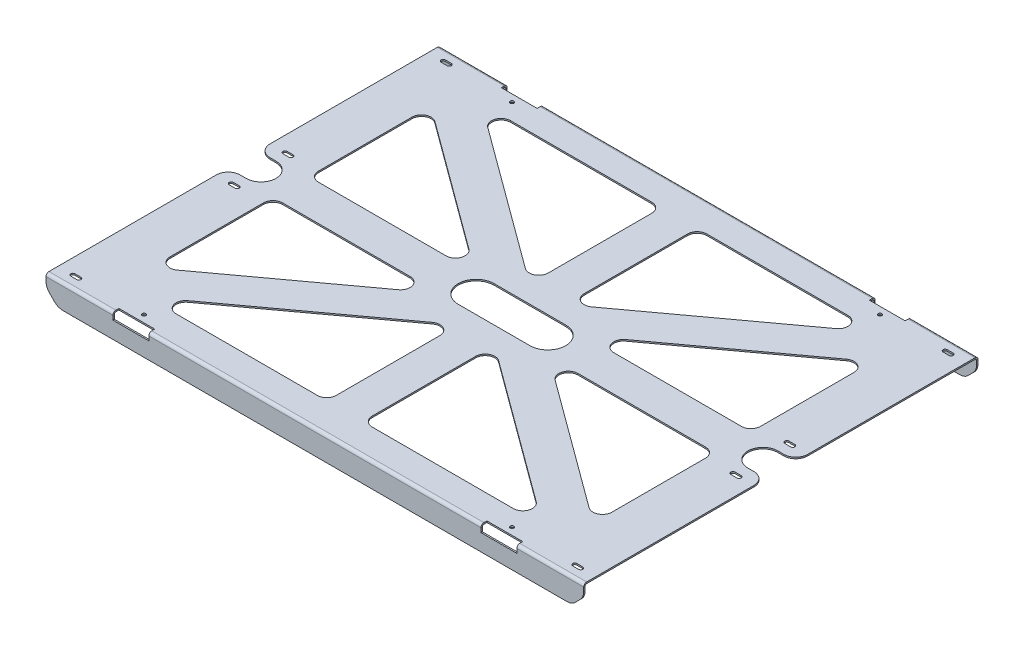
SolidWorks part; units mm, degrees
note: The reader was unsure of these and kept them because the rebuilt part matched: flange length of "Edge-Flange1".
material "1023 Carbon Steel Sheet (SS)"
ref_plane "Front Plane" through (0, 0, 0) normal (0, 0, 1) x (1, 0, 0)
ref_plane "Top Plane" through (0, 0, 0) normal (0, 1, 0) x (1, 0, 0)
ref_plane "Right Plane" through (0, 0, 0) normal (1, 0, 0) x (0, 0, -1)
sketch "Sketch1" plane through (0, 0, 0) normal (0, 1, 0) x (1, 0, 0)
  line L0 (-225, 165) -> (0, 0) construction
  line L1 (-225, -165) -> (225, -165)
  line L2 (-225, -165) -> (-225, -22.5)
  line L3 (-225, 165) -> (225, 165)
  line L4 (225, -165) -> (225, -22.5)
  line L5 (0, 165) -> (0, -165) construction
  line L6 (-225, 0) -> (225, 0) construction
  line L7 (-15, 132) -> (-15, 45.3883)
  line L8 (-172.2691, 107.7296) -> (-65.5259, 29.4512)
  line L9 (-145.8378, 125.5488) -> (-27.7309, 38.9371)
  line L10 (-185, 23) -> (-185, 101.2784)
  line L11 (-185, 125) -> (185, 125) construction
  line L12 (-185, -125) -> (-185, 125) construction
  line L13 (-185, -125) -> (185, -125) construction
  line L14 (185, -125) -> (185, 125) construction
  line L15 (-216.1295, 177.0961) -> (8.8705, 12.0961) construction
  line L16 (-233.8705, 152.9039) -> (-8.8705, -12.0961) construction
  line L17 (-141.1068, 140) -> (-23, 140)
  line L18 (-177, 15) -> (-70.2568, 15)
  line L19 (-15, 165) -> (-15, -165) construction
  line L20 (-225, 15) -> (225, 15) construction
  line L21 (177, 15) -> (70.2568, 15)
  line L22 (185, 23) -> (185, 101.2784)
  line L23 (172.2691, 107.7296) -> (65.5259, 29.4512)
  line L24 (145.8378, 125.5488) -> (27.7309, 38.9371)
  line L25 (141.1068, 140) -> (23, 140)
  line L26 (15, 132) -> (15, 45.3883)
  line L27 (-177, -15) -> (-70.2568, -15)
  line L28 (-185, -23) -> (-185, -101.2784)
  line L29 (-172.2691, -107.7296) -> (-65.5259, -29.4512)
  line L30 (-15, -132) -> (-15, -45.3883)
  line L31 (-145.8378, -125.5488) -> (-27.7309, -38.9371)
  line L32 (-141.1068, -140) -> (-23, -140)
  line L33 (15, -132) -> (15, -45.3883)
  line L34 (141.1068, -140) -> (23, -140)
  line L35 (145.8378, -125.5488) -> (27.7309, -38.9371)
  line L36 (172.2691, -107.7296) -> (65.5259, -29.4512)
  line L37 (185, -23) -> (185, -101.2784)
  line L38 (177, -15) -> (70.2568, -15)
  line L39 (-30, 0) -> (30, 0) construction
  line L40 (-30, 15) -> (30, 15)
  line L41 (-30, -15) -> (30, -15)
  line L42 (-225, 22.5) -> (-225, 165)
  line L43 (-225, -165) -> (-225, 165) construction
  line L44 (225, 22.5) -> (225, 165)
  line L45 (225, -165) -> (225, 165) construction
  line L46 (210, -12.5) -> (215, -12.5)
  line L47 (210, 12.5) -> (215, 12.5)
  line L48 (-212.5, 22.5) -> (-207.5, 22.5) construction
  line L49 (-212.5, 155) -> (-207.5, 155) construction
  line L50 (-212.5, 156.75) -> (-207.5, 156.75)
  line L51 (-212.5, 153.25) -> (-207.5, 153.25)
  line L52 (-212.5, -155) -> (-207.5, -155) construction
  line L53 (-212.5, -156.75) -> (-207.5, -156.75)
  line L54 (-212.5, -153.25) -> (-207.5, -153.25)
  line L55 (212.5, -155) -> (207.5, -155) construction
  line L56 (212.5, -156.75) -> (207.5, -156.75)
  line L57 (212.5, -153.25) -> (207.5, -153.25)
  line L58 (-212.5, 24.25) -> (-207.5, 24.25)
  line L59 (-212.5, 20.75) -> (-207.5, 20.75)
  line L60 (-212.5, -22.5) -> (-207.5, -22.5) construction
  line L61 (212.5, 155) -> (207.5, 155) construction
  line L62 (212.5, 156.75) -> (207.5, 156.75)
  line L63 (212.5, 153.25) -> (207.5, 153.25)
  line L64 (-210, 12.5) -> (-215, 12.5)
  line L65 (-210, -12.5) -> (-215, -12.5)
  line L66 (-212.5, -20.75) -> (-207.5, -20.75)
  line L67 (-212.5, -24.25) -> (-207.5, -24.25)
  line L68 (207.5, 22.5) -> (212.5, 22.5) construction
  line L69 (207.5, 24.25) -> (212.5, 24.25)
  line L70 (207.5, 20.75) -> (212.5, 20.75)
  line L71 (207.5, -22.5) -> (212.5, -22.5) construction
  line L72 (207.5, -20.75) -> (212.5, -20.75)
  line L73 (207.5, -24.25) -> (212.5, -24.25)
  arc A0 (-185, 23) -> (-177, 15) centre (-177, 23) ccw
  arc A1 (-172.2691, 107.7296) -> (-185, 101.2784) centre (-177, 101.2784) ccw
  arc A2 (-65.5259, 29.4512) -> (-70.2568, 15) centre (-70.2568, 23) cw
  arc A3 (-27.7309, 38.9371) -> (-15, 45.3883) centre (-23, 45.3883) ccw
  arc A4 (-15, 132) -> (-23, 140) centre (-23, 132) ccw
  arc A5 (-145.8378, 125.5488) -> (-141.1068, 140) centre (-141.1068, 132) cw
  arc A6 (185, 23) -> (177, 15) centre (177, 23) cw
  arc A7 (172.2691, 107.7296) -> (185, 101.2784) centre (177, 101.2784) cw
  arc A8 (65.5259, 29.4512) -> (70.2568, 15) centre (70.2568, 23) ccw
  arc A9 (145.8378, 125.5488) -> (141.1068, 140) centre (141.1068, 132) ccw
  arc A10 (15, 132) -> (23, 140) centre (23, 132) cw
  arc A11 (27.7309, 38.9371) -> (15, 45.3883) centre (23, 45.3883) cw
  arc A12 (-185, -23) -> (-177, -15) centre (-177, -23) cw
  arc A13 (-172.2691, -107.7296) -> (-185, -101.2784) centre (-177, -101.2784) cw
  arc A14 (-65.5259, -29.4512) -> (-70.2568, -15) centre (-70.2568, -23) ccw
  arc A15 (-15, -132) -> (-23, -140) centre (-23, -132) cw
  arc A16 (-27.7309, -38.9371) -> (-15, -45.3883) centre (-23, -45.3883) cw
  arc A17 (-145.8378, -125.5488) -> (-141.1068, -140) centre (-141.1068, -132) ccw
  arc A18 (27.7309, -38.9371) -> (15, -45.3883) centre (23, -45.3883) ccw
  arc A19 (15, -132) -> (23, -140) centre (23, -132) ccw
  arc A20 (145.8378, -125.5488) -> (141.1068, -140) centre (141.1068, -132) cw
  arc A21 (65.5259, -29.4512) -> (70.2568, -15) centre (70.2568, -23) cw
  arc A22 (172.2691, -107.7296) -> (185, -101.2784) centre (177, -101.2784) ccw
  arc A23 (185, -23) -> (177, -15) centre (177, -23) ccw
  arc A24 (-30, 15) -> (-30, -15) centre (-30, 0) ccw
  arc A25 (30, -15) -> (30, 15) centre (30, 0) ccw
  arc A26 (-210, -12.5) -> (-210, 12.5) centre (-210, 0) ccw
  arc A27 (-215, -12.5) -> (-225, -22.5) centre (-215, -22.5) ccw
  arc A28 (-215, 12.5) -> (-225, 22.5) centre (-215, 22.5) cw
  arc A29 (215, -12.5) -> (225, -22.5) centre (215, -22.5) cw
  arc A30 (210, -12.5) -> (210, 12.5) centre (210, 0) cw
  arc A31 (215, 12.5) -> (225, 22.5) centre (215, 22.5) ccw
  arc A32 (-212.5, 24.25) -> (-212.5, 20.75) centre (-212.5, 22.5) ccw
  arc A33 (-207.5, 20.75) -> (-207.5, 24.25) centre (-207.5, 22.5) ccw
  arc A34 (-212.5, 156.75) -> (-212.5, 153.25) centre (-212.5, 155) ccw
  arc A35 (-207.5, 153.25) -> (-207.5, 156.75) centre (-207.5, 155) ccw
  arc A36 (-212.5, -156.75) -> (-212.5, -153.25) centre (-212.5, -155) cw
  arc A37 (-207.5, -153.25) -> (-207.5, -156.75) centre (-207.5, -155) cw
  arc A38 (212.5, -156.75) -> (212.5, -153.25) centre (212.5, -155) ccw
  arc A39 (207.5, -153.25) -> (207.5, -156.75) centre (207.5, -155) ccw
  arc A40 (-212.5, -20.75) -> (-212.5, -24.25) centre (-212.5, -22.5) ccw
  arc A41 (-207.5, -24.25) -> (-207.5, -20.75) centre (-207.5, -22.5) ccw
  arc A42 (212.5, 156.75) -> (212.5, 153.25) centre (212.5, 155) cw
  arc A43 (207.5, 153.25) -> (207.5, 156.75) centre (207.5, 155) cw
  arc A44 (207.5, 24.25) -> (207.5, 20.75) centre (207.5, 22.5) ccw
  arc A45 (212.5, 20.75) -> (212.5, 24.25) centre (212.5, 22.5) ccw
  arc A46 (207.5, -20.75) -> (207.5, -24.25) centre (207.5, -22.5) ccw
  arc A47 (212.5, -24.25) -> (212.5, -20.75) centre (212.5, -22.5) ccw
  point P0 (0, 0)
  point P95 (0, 0)
  point P103 (-210, -22.5)
  point P104 (-225, -12.5)
  point P117 (-197.5, 0)
  point P120 (-210, 155)
  point P127 (-210, -155)
  point P134 (210, -155)
  point P139 (-210, 22.5)
  point P148 (210, 155)
  point P153 (-225, 12.5)
  point P157 (0, 0)
  point P158 (210, -22.5)
  point P165 (210, 22.5)
  point P174 (216.5035, 22.5)
  point P175 (0, 0)
  point P176 (0, 0)
  point P177 (-244.1151, 153.25)
  point P178 (244.8311, 22.5)
  point P179 (-231.402, 22.5)
  point P186 (0, 0)
  point P187 (0, 0)
  point P188 (0, 0)
  point P189 (-237.0247, -22.5)
  point P190 (0, 0)
  point P191 (-190.9514, 155)
  point P192 (0, 0)
  point P193 (0, 0)
  dimension "D9" = 8
  dimension "D10" = 15
  dimension "D11" = 60
  dimension "D12" = 25
  dimension "D13" = 15
  dimension "D15" = 2
  dimension "D16" = 15
  dimension "D17" = 1.75
  dimension "D18" = 5
  dimension "D21" = 10
  dimension "D1" = 450
  dimension "D2" = 330
  dimension "D6" = 25
  dimension "D14" = 2
  dimension "D19" = 10
  dimension "D3" = 40
  dimension "D4" = 15
  dimension "D5" = 15
  dimension "D7" = 15
  dimension "D8" = 15
base flange "Base-Flange1" sketch "Sketch1" thickness 1.2141 reverse thickness direction no parameters "D1"=1.27
edge flange "Edge-Flange1" sketch "Sketch10" flange profiles "Sketch10", "Sketch11" flange angle 90 flange length 20 flange position material inside bend radius 1.27 thickness 1.2141 relief rectangular parameters "D6"=10, "D8"=1
sketch "Sketch10" plane through (0, -1.2141, 165) normal (0, 0, 1) x (-1, 0, 0)
  line L2 (-225, 0) -> (-225, 18.7859)
  line L3 (-225, 18.7859) -> (225, 18.7859)
  line L4 (225, 18.7859) -> (225, 0)
  line L5 (225, 0) -> (-225, 0) construction
  line L6 (225, 0) -> (-225, 0)
sketch "Sketch11" plane through (0, -1.2141, -165) normal (0, 0, -1) x (1, 0, 0)
  line L0 (225, 0) -> (-225, 0) construction
  line L1 (225, 0) -> (-225, 0)
  line L2 (-225, 0) -> (-225, 18.7859)
  line L3 (-225, 18.7859) -> (225, 18.7859)
  line L4 (225, 18.7859) -> (225, 0)
bend "EdgeBend1" bend radius 1.27 bend angle 90 parameters "D5"=1
bend "EdgeBend2" bend radius 1.27 bend angle 90 parameters "D5"=2
chamfer "Chamfer1" distance 10 angle 45 4 edges at (225, -20, -164.3929) (-225, -20, -164.3929) (-225, -20, 164.3929) (225, -20, 164.3929)
fillet "Fillet1" radius 10 8 edges at (-225, -10, -164.3929) (-215, -20, -164.3929) (215, -20, -164.3929) (225, -10, -164.3929) (225, -10, 164.3929) (215, -20, 164.3929) (-215, -20, 164.3929) (-225, -10, 164.3929)
sketch "Sketch12" plane through (0, 0, 0) normal (0, 1, 0) x (1, 0, 0)
  line L1 (154, 154) -> (-154, 154) construction
  line L2 (154, 154) -> (154, -154) construction
  line L3 (154, -154) -> (-154, -154) construction
  line L4 (-154, 154) -> (-154, -154) construction
  line L5 (0, -154) -> (0, 154) construction
  line L6 (154, 0) -> (-154, 0) construction
  circle A0 centre (154, -154) radius 1.55
  circle A1 centre (-154, -154) radius 1.55
  circle A2 centre (-154, 154) radius 1.55
  circle A3 centre (154, 154) radius 1.55
  point P0 (0, 0)
  dimension "D2" = 3.1
  dimension "D1" = 308
extrude "Cut-Extrude1" cut sketch "Sketch12" against normal up to surface (1.2141 mm away) normal cut yes up to face at (210, -1.2141, -22.5)
sketch "Sketch13" plane through (0, 0, 165) normal (0, 0, 1) x (1, 0, 0)
  line L0 (0, -20) -> (0, 0) construction
  line L1 (-210.8579, -20) -> (210.8579, -20) construction
  line L2 (-225, 0) -> (225, 0) construction
  line L3 (-169, 6) -> (-139, 6)
  line L4 (-169, 6) -> (-169, -6)
  line L5 (-169, -6) -> (-139, -6)
  line L6 (-139, 6) -> (-139, -6)
  line L7 (-154, -6) -> (-154, 6) construction
  line L8 (-169, 0) -> (-139, 0) construction
  line L9 (169, 0) -> (139, 0) construction
  line L10 (154, -6) -> (154, 6) construction
  line L11 (139, 6) -> (139, -6)
  line L12 (169, -6) -> (139, -6)
  line L13 (169, 6) -> (169, -6)
  line L14 (169, 6) -> (139, 6)
  point P5 (-154, 0)
  point P11 (0, 0)
  point P20 (154, 0)
  dimension "D1" = 154
  dimension "D2" = 30
  dimension "D3" = 12
extrude "Cut-Extrude2" cut sketch "Sketch13" against normal blind 5 normal cut yes
mirror "Mirror1" about plane through (0, 0, 0) normal (0, 0, 1) of "Cut-Extrude2"
sketch "Bend-Lines1" [suppressed] plane through (0, 0, 0) normal (0, 1, 0) x (1, 0, 0)
sketch "Bounding-Box1" [suppressed] plane through (0, 0, 0) normal (0, 1, 0) x (1, 0, 0)
sheet metal parameters "Sheet-Metal1" thickness 1.2141 parameters "D1"=1.27
flat pattern "Flat-Pattern1" [suppressed]
sketch "Bend-Lines2" plane through (0, 0, 0) normal (0, 1, 0) x (1, 0, 0)
sketch "Bounding-Box2" [suppressed] plane through (0, 0, 0) normal (0, 1, 0) x (1, 0, 0)
sheet metal parameters "Sheet-Metal2" thickness 1.2141 parameters "D1"=1.27
flat pattern "Flat-Pattern1" [suppressed]
sketch "Bend-Lines2" plane through (0, 0, 0) normal (0, 1, 0) x (1, 0, 0)
sketch "Bounding-Box2" [suppressed] plane through (0, 0, 0) normal (0, 1, 0) x (1, 0, 0)
bend of the flat pattern "Flatten-<EdgeBend1>1"
bend of the flat pattern "Flatten-<EdgeBend2>1"
sheet metal parameters "Sheet-Metal3" thickness 1.2141 parameters "D1"=1.27
flat pattern "Flat-Pattern1" [suppressed]
sketch "Bend-Lines2" plane through (0, 0, 0) normal (0, 1, 0) x (1, 0, 0)
sketch "Bounding-Box2" [suppressed] plane through (0, 0, 0) normal (0, 1, 0) x (1, 0, 0)
bend of the flat pattern "Flatten-<EdgeBend1>1"
bend of the flat pattern "Flatten-<EdgeBend2>1"
sheet metal parameters "Sheet-Metal4" thickness 1.2141 parameters "D1"=1.27
flat pattern "Flat-Pattern1" [suppressed]
sketch "Bend-Lines2" plane through (0, 0, 0) normal (0, 1, 0) x (1, 0, 0)
sketch "Bounding-Box2" [suppressed] plane through (0, 0, 0) normal (0, 1, 0) x (1, 0, 0)
bend of the flat pattern "Flatten-<EdgeBend1>1"
bend of the flat pattern "Flatten-<EdgeBend2>1"
sheet metal parameters "Sheet-Metal5" thickness 1.2141 parameters "D1"=1.27
flat pattern "Flat-Pattern1"
sketch "Bend-Lines2" plane through (0, 0, 0) normal (0, 1, 0) x (1, 0, 0)
  line L0 (225, 163.9901) -> (-225, 163.9901) construction
  line L1 (-225, -163.9901) -> (225, -163.9901) construction
  line L2 (-169, 163.9901) -> (-225, 163.9901) construction
  line L3 (225, 163.9901) -> (169, 163.9901) construction
  line L4 (139, 163.9901) -> (-139, 163.9901) construction
  line L5 (-225, -163.9901) -> (-169, -163.9901) construction
  line L6 (-139, -163.9901) -> (139, -163.9901) construction
  line L7 (169, -163.9901) -> (225, -163.9901) construction
sketch3d "Bounding-Box2" [suppressed]
  line L0 (-10, 160.4802, 0) -> (440, 160.4802, 0) construction
  line L1 (-10, -205.4802, 0) -> (440, -205.4802, 0) construction
  line L2 (-10, 160.4802, 0) -> (-10, -205.4802, 0) construction
  line L3 (440, 160.4802, 0) -> (440, -205.4802, 0) construction
bend of the flat pattern "Flatten-<EdgeBend1>1"
bend of the flat pattern "Flatten-<EdgeBend2>1"
